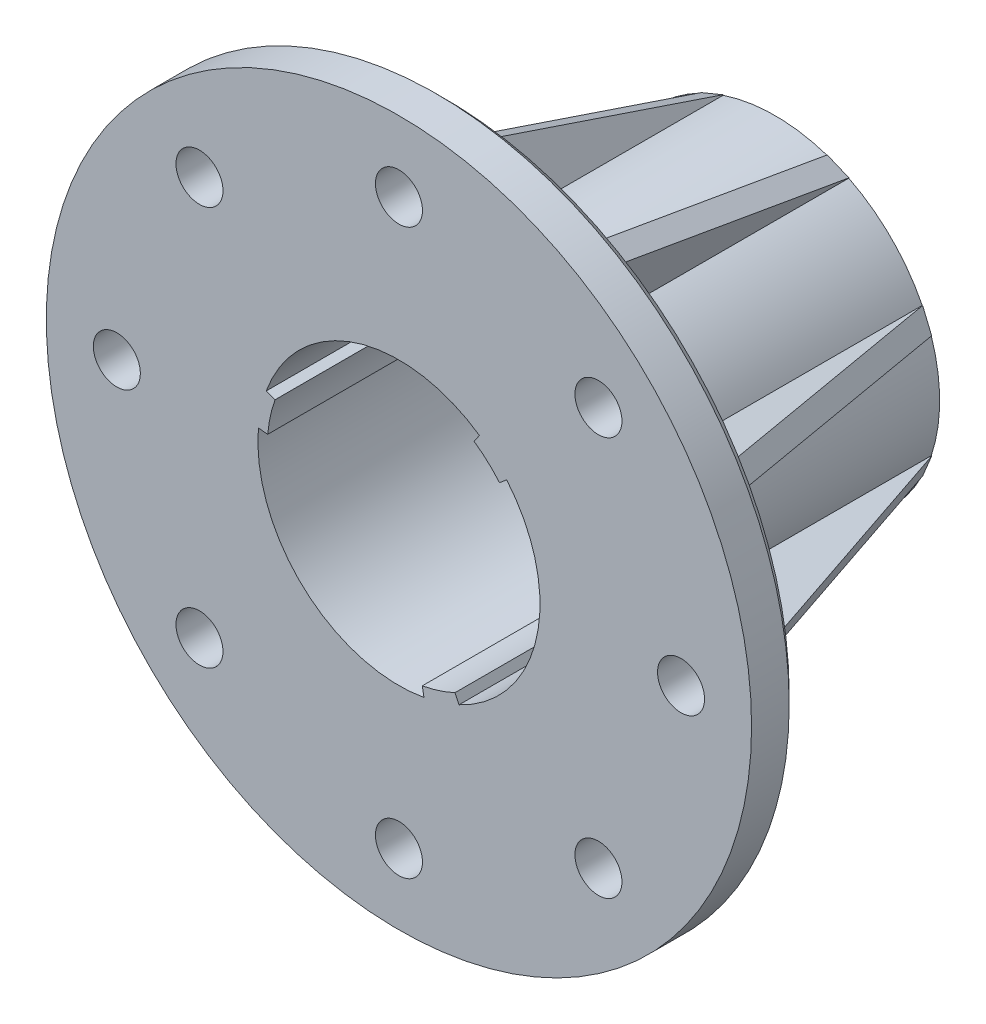
SolidWorks part; units mm, degrees
other "Weld Folder"
material "2024-T4"
ref_plane "Front Plane" through (0, 0, 0) normal (0, 0, 1) x (1, 0, 0)
ref_plane "Top Plane" through (0, 0, 0) normal (0, 1, 0) x (1, 0, 0)
ref_plane "Right Plane" through (0, 0, 0) normal (1, 0, 0) x (0, 0, -1)
sketch "Sketch1" plane through (0, 0, 0) normal (0, 0, 1) x (1, 0, 0)
  circle A0 centre (0, 0) radius 22.225
  circle A1 centre (0, 0) radius 15.875 construction
  circle A2 centre (0, 0) radius 17.78
  arc A4 (-11.0441, -13.934) -> (-7.0614, -16.3176) centre (0, 0) ccw construction
  dimension "D1" = 44.45
extrude "Boss-Extrude1" add sketch "Sketch1" along normal blind 50.8
sketch "Sketch2" plane through (0, 0, 50.8) normal (0, 0, 1) x (1, 0, 0)
  circle A0 centre (0, 0) radius 47.625
  circle A1 centre (0, 0) radius 22.225 construction
  circle A2 centre (0, 0) radius 22.225
  dimension "D1" = 95.25
extrude "Boss-Extrude2" add sketch "Sketch2" against normal blind 6.35 separate body
sketch "Sketch3" plane through (0, 0, 50.8) normal (0, 0, 1) x (1, 0, 0)
  circle A0 centre (-38.1, 0) radius 3.175
  circle A1 centre (-26.9408, 26.9408) radius 3.175
  circle A2 centre (0, 38.1) radius 3.175
  circle A3 centre (26.9408, 26.9408) radius 3.175
  circle A4 centre (38.1, 0) radius 3.175
  circle A5 centre (26.9408, -26.9408) radius 3.175
  circle A6 centre (0, -38.1) radius 3.175
  circle A7 centre (-26.9408, -26.9408) radius 3.175
  point P20 (0, 0)
  dimension "D1" = 6.35
  dimension "D2" = 38.1
  dimension "D3" = 8
extrude "Cut-Extrude1" cut sketch "Sketch3" against normal through all
chamfer "Chamfer1" distance 1.27 angle 45 1 edges at (47.625, 0, 44.45)
ref_axis "Axis1" through (0, 0, 50.8) along (0, 0, -1)
ref_plane "Plane1" through (0, 0, 0) normal (0.9239, -0.3827, 0) x (0, 0, -1)
sketch "Sketch4" plane through (0, 0, 0) normal (0.9239, -0.3827, 0) x (0, 0, -1)
  line L0 (-44.45, 34.925) -> (0, 22.225)
  line L1 (0, 22.225) -> (-50.8, 22.225) construction
  line L2 (0, -22.225) -> (0, 22.225) construction
  line L3 (-44.45, -46.355) -> (-44.45, 46.355) construction
  line L4 (0, 21.463) -> (-44.45, 21.463)
  line L6 (-44.45, 21.463) -> (-44.45, 34.925)
  line L7 (0, 22.225) -> (0, 21.463)
  dimension "D1" = 12.7
  dimension "D2" = 0.762
extrude "Boss-Extrude3" add sketch "Sketch4" along normal mid plane 3.175
pattern_circular "CirPattern1" count 8 over 360 about axis through (0, 0, 44.45) along (0, 0, 1) of "Boss-Extrude3" reverse direction yes
sketch "Sketch5" plane through (0, 0, 0) normal (0, 0, -1) x (-1, 0, 0)
  line L26 (7.5658, -17.4832) -> (7.0614, -16.3176)
  line L27 (11.0441, -13.934) -> (11.833, -14.9293)
  line L34 (11.358, 15.2938) -> (10.6008, 14.2742)
  line L35 (6.5451, 16.5315) -> (7.0126, 17.7123)
  line L42 (-18.9238, 2.1894) -> (-17.6622, 2.0434)
  line L43 (-17.5892, -2.5975) -> (-18.8456, -2.783)
  line L50 (7.5658, -17.4832) -> (7.0614, -16.3176) construction
  line L51 (11.0441, -13.934) -> (11.833, -14.9293) construction
  line L58 (11.358, 15.2938) -> (10.6008, 14.2742) construction
  line L59 (6.5451, 16.5315) -> (7.0126, 17.7123) construction
  line L66 (-18.9238, 2.1894) -> (-17.6622, 2.0434) construction
  line L67 (-17.5892, -2.5975) -> (-18.8456, -2.783) construction
  arc A1 (15.4681, -11.1194) -> (17.8189, -6.7371) centre (0, 0) ccw
  arc A2 (14.4369, -10.3781) -> (16.631, -6.288) centre (0, 0) ccw
  arc A3 (7.3136, -16.2061) -> (11.2589, -13.761) centre (0, 0) ccw construction
  arc A4 (7.0614, -16.3176) -> (11.0441, -13.934) centre (0, 0) ccw construction
  arc A5 (-10.3781, -14.4369) -> (-6.288, -16.631) centre (0, 0) ccw construction
  arc A6 (-16.2061, -7.3136) -> (-13.761, -11.2589) centre (0, 0) ccw
  arc A7 (-17.6918, 1.7693) -> (-17.5468, -2.87) centre (0, 0) ccw construction
  arc A8 (-17.6622, 2.0434) -> (-17.5892, -2.5975) centre (0, 0) ccw construction
  arc A9 (-7.3136, 16.2061) -> (-11.2589, 13.761) centre (0, 0) ccw construction
  arc A10 (1.7693, 17.6918) -> (-2.87, 17.5468) centre (0, 0) ccw
  arc A11 (10.3781, 14.4369) -> (6.288, 16.631) centre (0, 0) ccw construction
  arc A12 (10.6008, 14.2742) -> (6.5451, 16.5315) centre (0, 0) ccw construction
  arc A13 (17.6918, -1.7693) -> (17.5468, 2.87) centre (0, 0) ccw construction
  arc A14 (18.9554, -1.8957) -> (18.8002, 3.075) centre (0, 0) ccw construction
  arc A15 (17.5161, 7.4891) -> (7.0126, 17.7123) centre (0, 0) ccw construction
  arc A16 (-15.2439, 11.4248) -> (6.7371, 17.8189) centre (0, 0) ccw construction
  arc A17 (1.8957, 18.9554) -> (-3.075, 18.8002) centre (0, 0) ccw
  arc A18 (-7.836, 17.3637) -> (-12.0631, 14.744) centre (0, 0) ccw construction
  arc A19 (-15.2439, 11.4248) -> (-17.6814, 7.0902) centre (0, 0) ccw construction
  arc A20 (-18.9554, 1.8957) -> (-18.8002, -3.075) centre (0, 0) ccw construction
  arc A21 (-17.3637, -7.836) -> (-14.744, -12.0631) centre (0, 0) ccw
  arc A22 (-11.1194, -15.4681) -> (-17.6814, 7.0902) centre (0, 0) ccw construction
  arc A23 (7.5658, -17.4832) -> (11.833, -14.9293) centre (0, 0) ccw construction
  arc A25 (-18.8456, -2.783) -> (7.5658, -17.4832) centre (0, 0) ccw
  arc A26 (7.0614, -16.3176) -> (11.0441, -13.934) centre (0, 0) ccw
  arc A27 (11.833, -14.9293) -> (11.358, 15.2938) centre (0, 0) ccw
  arc A34 (10.6008, 14.2742) -> (6.5451, 16.5315) centre (0, 0) ccw
  arc A35 (7.0126, 17.7123) -> (-18.9238, 2.1894) centre (0, 0) ccw
  arc A42 (-17.6622, 2.0434) -> (-17.5892, -2.5975) centre (0, 0) ccw
  arc A49 (-18.8456, -2.783) -> (7.5658, -17.4832) centre (0, 0) ccw construction
  arc A51 (11.833, -14.9293) -> (11.358, 15.2938) centre (0, 0) ccw construction
  arc A59 (7.0126, 17.7123) -> (-18.9238, 2.1894) centre (0, 0) ccw construction
  arc A72 (17.5161, 7.4891) -> (12.0631, -14.744) centre (0, 0) ccw construction
  dimension "D1" = 0
extrude "Cut-Extrude2" [suppressed] cut sketch "Sketch5" against normal through all
sketch "Sketch6" plane through (0, 0, 0) normal (0, 0, -1) x (-1, 0, 0)
  line L6 (16.7295, 6.021) -> (17.9245, 6.451)
  line L7 (18.9834, 1.592) -> (17.7178, 1.4859)
  line L8 (-3.1504, -17.4987) -> (-3.3755, -18.7486)
  line L9 (-8.1129, -17.2361) -> (-7.5721, -16.087)
  line L10 (-13.5791, 11.4777) -> (-14.549, 12.2975)
  line L11 (-10.8704, 15.6441) -> (-10.1457, 14.6011)
  line L12 (16.7295, 6.021) -> (17.9245, 6.451)
  line L13 (18.9834, 1.592) -> (17.7178, 1.4859)
  line L14 (-3.1504, -17.4987) -> (-3.3755, -18.7486)
  line L15 (-8.1129, -17.2361) -> (-7.5721, -16.087)
  line L16 (-13.5791, 11.4777) -> (-14.549, 12.2975)
  line L17 (-10.8704, 15.6441) -> (-10.1457, 14.6011)
  arc A0 (-14.549, 12.2975) -> (-8.1129, -17.2361) centre (0, 0) ccw
  circle A1 centre (0, 0) radius 17.78 construction
  arc A2 (-13.5791, 11.4777) -> (-7.5721, -16.087) centre (0, 0) ccw
  arc A3 (16.7295, 6.021) -> (-10.1457, 14.6011) centre (0, 0) ccw
  arc A4 (-3.1504, -17.4987) -> (17.7178, 1.4859) centre (0, 0) ccw
  arc A5 (17.9245, 6.451) -> (-10.8704, 15.6441) centre (0, 0) ccw
  arc A6 (17.7178, 1.4859) -> (16.7295, 6.021) centre (0, 0) ccw
  arc A7 (-3.3755, -18.7486) -> (18.9834, 1.592) centre (0, 0) ccw
  arc A8 (-7.5721, -16.087) -> (-3.1504, -17.4987) centre (0, 0) ccw
  arc A9 (-14.549, 12.2975) -> (-8.1129, -17.2361) centre (0, 0) ccw
  arc A10 (-10.1457, 14.6011) -> (-13.5791, 11.4777) centre (0, 0) ccw
  arc A11 (17.9245, 6.451) -> (-10.8704, 15.6441) centre (0, 0) ccw
  arc A13 (-3.3755, -18.7486) -> (18.9834, 1.592) centre (0, 0) ccw
  arc A15 (-14.549, 12.2975) -> (-8.1129, -17.2361) centre (0, 0) ccw
  arc A17 (17.9245, 6.451) -> (-10.8704, 15.6441) centre (0, 0) ccw
  arc A18 (-3.3755, -18.7486) -> (18.9834, 1.592) centre (0, 0) ccw
  circle M47 centre (0, 0) radius 17.78
  dimension "D1" = 0
extrude "Cut-Extrude3" cut sketch "Sketch6" against normal through all contours L16 A0 L15 M47 | L12 A5 L17 M47 | L14 A13 L13 M47 region at (-5.5036, 17.2388, 0) region at (-18.3761, 1.2352, 0) region at (17.6819, -3.8533, 0)
